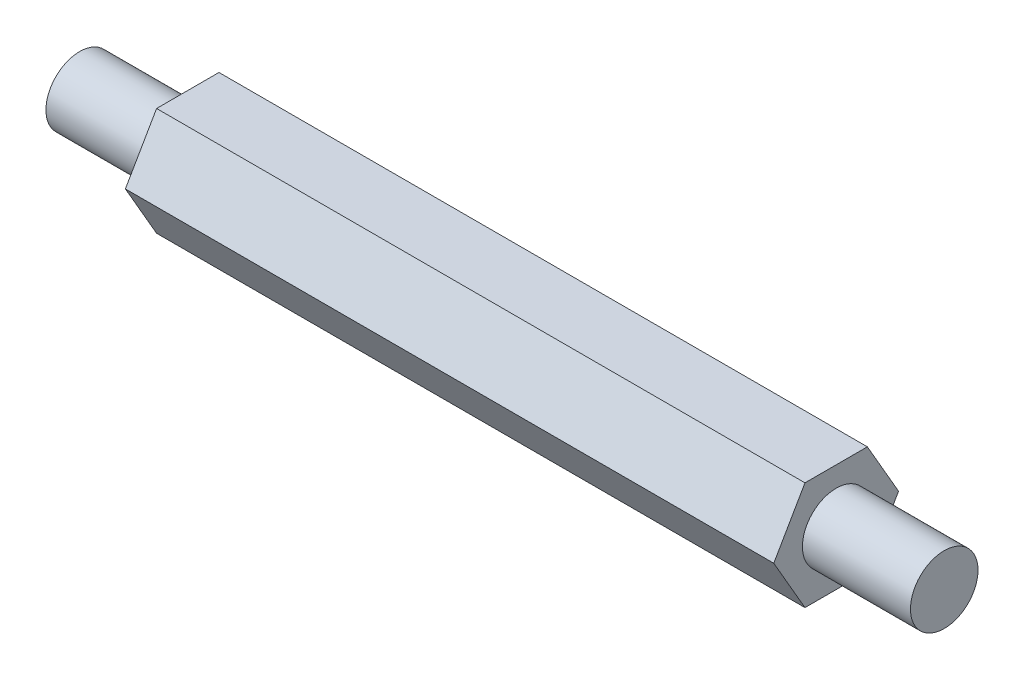
SolidWorks part; units mm, degrees
ref_plane "Front Plane" through (0, 0, 0) normal (0, 0, 1) x (1, 0, 0)
ref_plane "Top Plane" through (0, 0, 0) normal (0, 1, 0) x (1, 0, 0)
ref_plane "Right Plane" through (0, 0, 0) normal (1, 0, 0) x (0, 0, -1)
sketch "Sketch1" plane through (0, 0, 0) normal (1, 0, 0) x (0, 0, -1)
  line L1 (14.6647, 0) -> (7.3323, 12.7)
  line L2 (7.3323, 12.7) -> (-7.3323, 12.7)
  line L3 (-7.3323, 12.7) -> (-14.6647, 0)
  line L4 (-14.6647, 0) -> (-7.3323, -12.7)
  line L5 (-7.3323, -12.7) -> (7.3323, -12.7)
  line L6 (7.3323, -12.7) -> (14.6647, 0)
  circle A0 centre (0, 0) radius 12.7 construction
extrude "Boss-Extrude1" add sketch "Sketch1" along normal blind 203.2
sketch "Sketch2" plane through (203.2, 0, 0) normal (1, 0, 0) x (0, 0, -1)
  circle A0 centre (0, 0) radius 7.9375
  dimension "D1" = 15.875
extrude "Cut-Extrude1" cut sketch "Sketch2" against normal blind 25.4 flip side to cut
extrude "Cut-Extrude3" cut sketch "Sketch2<2>" against normal blind 25.4 from offset 177.8 flip side to cut offset against normal yes
sketch "Sketch2<2>" plane through (203.2, 0, 0) normal (1, 0, 0) x (0, 0, -1) same geometry as "Sketch2"
